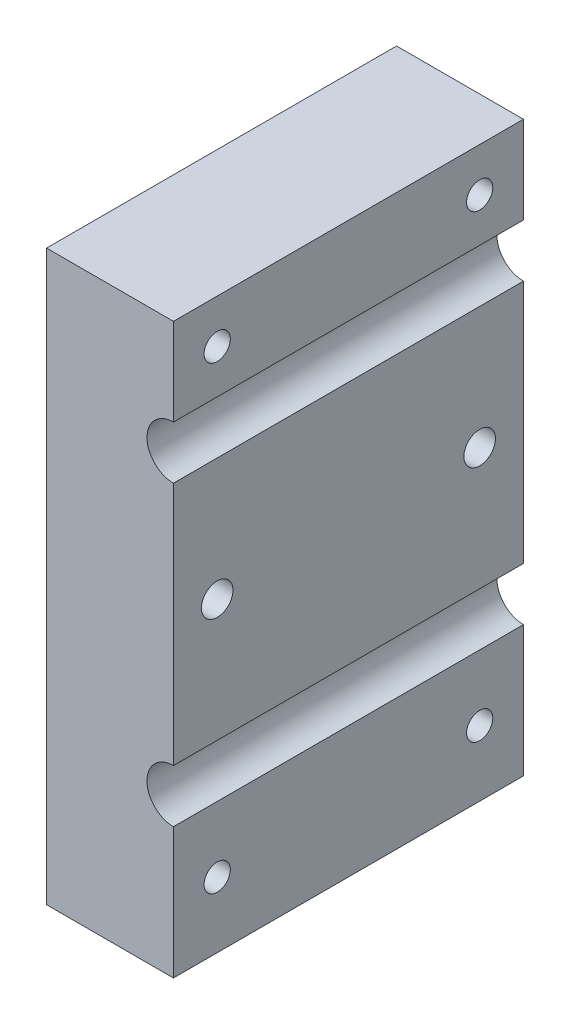
SolidWorks part; units mm, degrees
ref_plane "前视基准面" through (0, 0, 0) normal (0, 0, 1) x (1, 0, 0)
ref_plane "上视基准面" through (0, 0, 0) normal (0, 1, 0) x (1, 0, 0)
ref_plane "右视基准面" through (0, 0, 0) normal (1, 0, 0) x (0, 0, -1)
sketch "草图1" plane through (0, 0, 0) normal (0, 0, 1) x (1, 0, 0)
  line L1 (0, 0) -> (29, 0)
  line L2 (0, 0) -> (0, 65)
  line L3 (0, 65) -> (29, 65)
  line L4 (29, 0) -> (29, 65)
extrude "凸台-拉伸1" add sketch "草图1" along normal blind 40
sketch "草图2" plane through (0, 0, 40) normal (0, 0, 1) x (1, 0, 0)
  line L0 (0, 0) -> (29, 0) construction
  circle A0 centre (14.5, 52) radius 3.005
  circle A1 centre (14.5, 18) radius 3.005
  circle A2 centre (14.5, 52) radius 3.025
  circle A3 centre (14.5, 18) radius 3.025
  dimension "D1" = 0.02
  dimension "D2" = 34
  dimension "D3" = 18
extrude "切除-拉伸3" cut sketch "草图2" against normal through all
sketch "草图6" plane through (0, 0, 40) normal (0, 0, 1) x (1, 0, 0)
  line L0 (29, 65) -> (0, 65) construction
  line L1 (14.5, 65) -> (29, 65)
  line L2 (14.5, 65) -> (14.5, 0)
  line L3 (14.5, 0) -> (29, 0)
  line L4 (29, 65) -> (29, 0)
extrude "切除-拉伸4" cut sketch "草图6" against normal through all
sketch "草图7" plane through (14.5, 0, 0) normal (1, 0, 0) x (0, 0, -1)
  line L0 (-40, 65) -> (-40, 55.025) construction
  circle A0 centre (-35, 60.0125) radius 1.5
  circle A2 centre (-5, 60.0125) radius 1.5
  dimension "D1" = 3
  dimension "D3" = 30
  dimension "D2" = 5
extrude "切除-拉伸5" cut sketch "草图7" against normal through all
sketch "草图8" plane through (14.5, 0, 0) normal (1, 0, 0) x (0, 0, -1)
  line L0 (-40, 48.975) -> (-40, 21.025) construction
  circle A0 centre (-35, 35) radius 1.8048
  circle A3 centre (-5, 35) radius 1.8048
  dimension "D2" = 30
  dimension "D1" = 5
extrude "切除-拉伸6" cut sketch "草图8" against normal through all
sketch "草图9" plane through (14.5, 0, 0) normal (1, 0, 0) x (0, 0, -1)
  line L0 (-40, 14.975) -> (-40, 0) construction
  circle A0 centre (-35, 7.4875) radius 1.5
  circle A3 centre (-5, 7.4875) radius 1.5
  dimension "D5" = 3
  dimension "D2" = 30
  dimension "D1" = 5
extrude "切除-拉伸7" cut sketch "草图9" against normal through all
